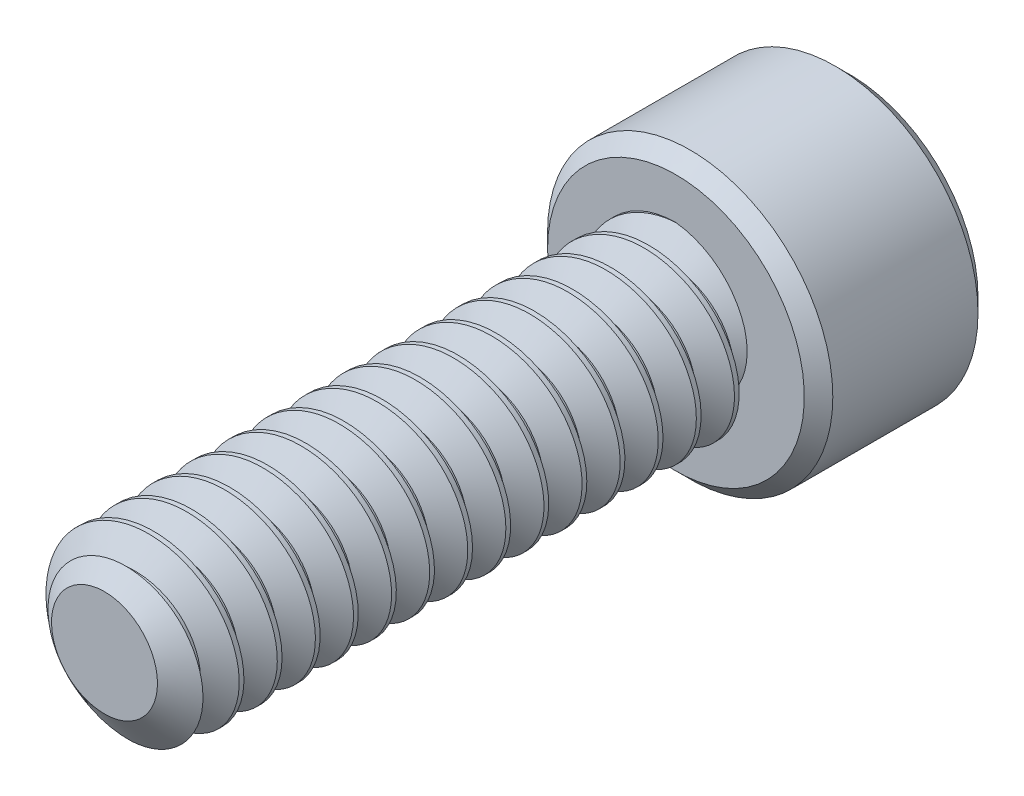
SolidWorks part; units mm, degrees
other "DetailItem1"
ref_plane "Front Plane" through (0, 0, 0) normal (0, 0, 1) x (1, 0, 0)
ref_plane "Top Plane" through (0, 0, 0) normal (0, 1, 0) x (1, 0, 0)
ref_plane "Right Plane" through (0, 0, 0) normal (1, 0, 0) x (0, 0, -1)
sketch "Sketch1" plane through (0, 0, 0) normal (0, 0, 1) x (1, 0, 0)
  circle A0 centre (0, 0) radius 2.413
  dimension "OD" = 4.826
extrude "Extrude1" add sketch "Sketch1" against normal blind 15.875
sketch "Sketch2" plane through (0, 0, 0) normal (0, 0, 1) x (1, 0, 0)
  circle A0 centre (0, 0) radius 2.413 construction
  circle A1 centre (0, 0) radius 2.413
curve "Helix/Spiral1" pitch 1.0583 height 16.9333 turns 16 parameters "pitch"=1.0583
sketch "Sketch3" plane through (0, 0, 0) normal (1, 0, 0) x (0, 0, -1)
  line L0 (-0.926, 2.413) -> (-0.5292, 1.7256)
  line L1 (-0.5292, 1.7256) -> (-0.3969, 1.7256)
  line L2 (-0.3969, 1.7256) -> (0, 2.413)
  line L3 (-0.926, 2.413) -> (0, 2.413)
  line L4 (-0.463, 2.413) -> (-0.463, 1.7256) construction
  line L5 (-0.7276, 2.0693) -> (-0.1984, 2.0693) construction
  line L6 (0, 2.413) -> (0, -2.413) construction
  dimension "D1" = 0.1323
  dimension "D2" = 0.5292
  dimension "D3" = 60
sweep "Cut-Sweep1" cut profiles "Sketch3" path "Helix/Spiral1"
sketch "Sketch4" plane through (0, 0, 0) normal (1, 0, 0) x (0, 0, -1)
  line L0 (0.6592, 2.413) -> (0, 1.4716)
  line L1 (0, 1.4716) -> (0, 2.413)
  line L2 (0.6592, 2.413) -> (0, 2.413)
  line L3 (-0.926, 2.413) -> (0, 2.413) construction
  line L4 (0, 0) -> (7.0209, 0) construction
  dimension "D1" = 55
  dimension "D2" = 0.254
revolve "Cut-Revolve1" cut sketch "Sketch4" angle 360 about L4
sketch "Sketch6" plane through (0, 0, -15.875) normal (0, 0, -1) x (-1, 0, 0)
  circle A0 centre (0, 0) radius 3.9624
  dimension "head dia" = 7.9248
extrude "Extrude2" add sketch "Sketch6" along normal blind 4.826
sketch "Sketch7" plane through (0, 0, -20.701) normal (0, 0, -1) x (-1, 0, 0)
  line L1 (0, 2.2914) -> (-1.9844, 1.1457)
  line L2 (-1.9844, 1.1457) -> (-1.9844, -1.1457)
  line L3 (-1.9844, -1.1457) -> (0, -2.2914)
  line L4 (0, -2.2914) -> (1.9844, -1.1457)
  line L5 (1.9844, -1.1457) -> (1.9844, 1.1457)
  line L6 (1.9844, 1.1457) -> (0, 2.2914)
  circle A0 centre (0, 0) radius 1.9844 construction
  dimension "hex dia" = 3.9688
extrude "Cut-Extrude1" cut sketch "Sketch7" against normal blind 2.9766
sketch "Sketch8" plane through (0, 0, -20.701) normal (0, 0, -1) x (-1, 0, 0)
  circle A0 centre (0, 0) radius 2.2914
extrude "Cut-Extrude2" cut sketch "Sketch8" against normal through all draft 45
chamfer "Chamfer1" distance 0.3962 angle 45 2 edges at (-3.9624, 0, -20.701) (-3.9624, 0, -15.875)
sketch "Sketch10" plane through (0, 0, -15.875) normal (0, 0, 1) x (1, 0, 0)
  circle A0 centre (0, 0) radius 2.413
extrude "Partial Thread" [suppressed] add sketch "Sketch10" along normal offset from surface (19.05 mm away) 2.54
sketch "Sketch9" plane through (0, 0, 0) normal (1, 0, 0) x (0, 0, -1)
  line L0 (0, 2.413) -> (0, -2.413) construction
  line L1 (1.5875, 2.413) -> (1.5875, -2.413) construction
  dimension "D1" = 1.5875
equation "\"D3@Helix/Spiral1\" = \"screw length@Extrude1\"+\"pitch@Helix/Spiral1\""
equation "\"D1@Sketch3\" = \"pitch@Helix/Spiral1\"*.125"
equation "\"D2@Sketch3\" = \"pitch@Helix/Spiral1\"*.5"
equation "\"D1@Cut-Extrude1\" = \"hex dia@Sketch7\"*.75"
equation "\"D1@Chamfer1\" = \"head dia@Sketch6\"*.05"
equation "\"D1@Sketch9\" = \"pitch@Helix/Spiral1\"*1.5"
